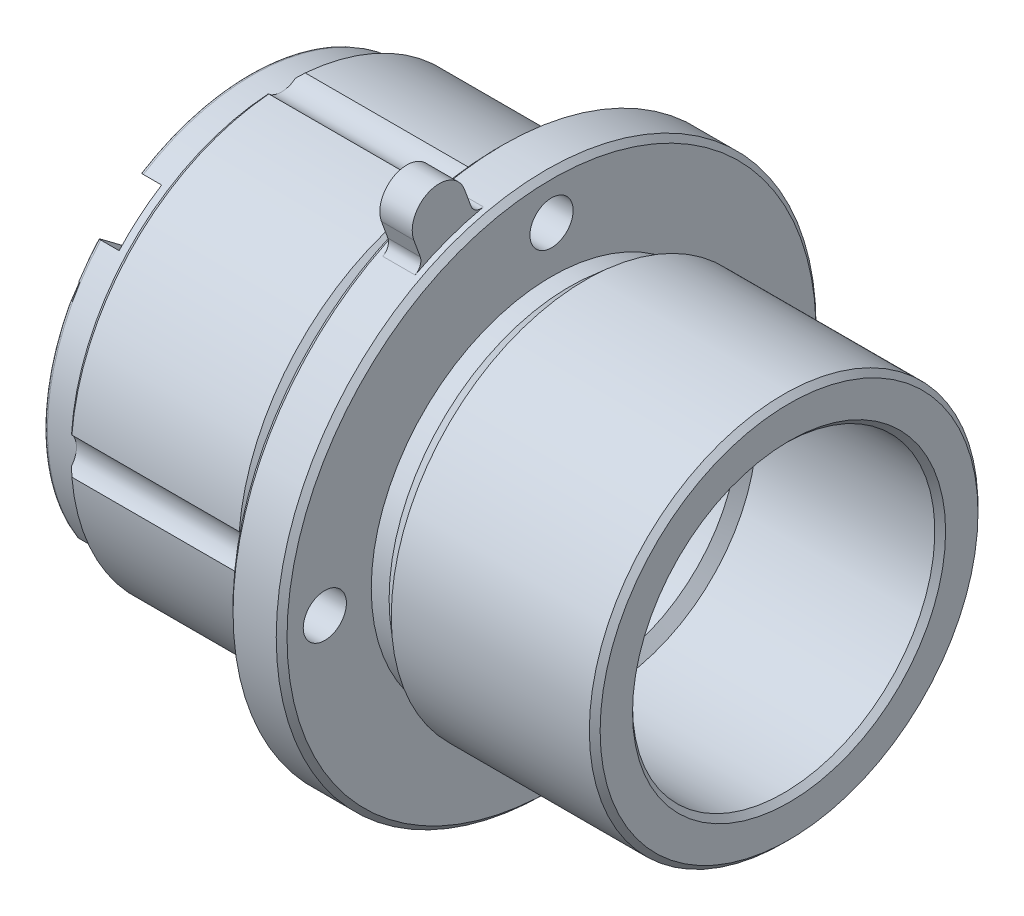
SolidWorks part; units mm, degrees
note: '?' marks a value the reader was unsure of.
ref_plane "Plane1" through (0, 0, 0) normal (0, 0, 1) x (1, 0, 0)
ref_plane "Plane2" through (0, 0, 0) normal (0, 1, 0) x (1, 0, 0)
ref_plane "Plane3" through (0, 0, 0) normal (1, 0, 0) x (0, 0, -1)
sketch "Sketch1" plane through (0, 0, 0) normal (0, 0, 1) x (1, 0, 0)
  line L0 (0, 35.56) -> (0, 48.26)
  line L1 (0, 48.26) -> (7.62, 48.26)
  line L2 (7.62, 48.26) -> (7.62, 50.8)
  line L3 (7.62, 50.8) -> (48.26, 50.8)
  line L4 (48.26, 50.8) -> (50.8, 48.26)
  line L5 (50.8, 48.26) -> (58.42, 48.26)
  line L6 (58.42, 48.26) -> (58.42, 63.5)
  line L7 (58.42, 63.5) -> (71.12, 63.5)
  line L8 (71.12, 63.5) -> (71.12, 42.4161)
  line L9 (71.12, 42.4161) -> (75.3191, 42.4161)
  line L10 (75.3191, 42.4161) -> (79.1291, 45.72)
  line L11 (79.1291, 45.72) -> (127, 45.72)
  line L12 (127, 45.72) -> (127, 35.56)
  line L13 (127, 35.56) -> (83.82, 35.56)
  line L14 (83.82, 35.56) -> (81.915, 33.02)
  line L15 (81.915, 33.02) -> (63.5, 33.02)
  line L16 (63.5, 33.02) -> (63.5, 30.48)
  line L17 (63.5, 30.48) -> (38.1, 30.48)
  line L18 (38.1, 30.48) -> (38.1, 38.1)
  line L19 (38.1, 38.1) -> (10.16, 38.1)
  line L20 (10.16, 38.1) -> (10.16, 35.56)
  line L21 (10.16, 35.56) -> (0, 35.56)
  line L22 (0, 0) -> (127, 0) construction
revolve "Base-Revolve" add sketch "Sketch1" angle 360 about L22
chamfer "Chamfer1" distance 1.27 angle 45 7 edges at (38.1, 0, 30.48) (127, 0, 35.56) (127, 0, 45.72) (71.12, 0, 63.5) (58.42, 0, 63.5) (7.62, 0, 50.8) (0, 0, 35.56)
fillet "Fillet1" radius 0.762 1 edges at (0, 0, 48.26)
sketch "Sketch2" plane through (71.12, 0, 0) normal (1, 0, 0) x (0, 0, -1)
  circle A0 centre (53.34, 0) radius 5.08
extrude "Cut-Extrude1" cut sketch "Sketch2" against normal through all
ref_axis "Axis1" through (-50, 0, 0) along (1, 0, 0)?
pattern_circular "CirPattern1" count 4 every 90 about axis through (0, 0, 0) along (1, 0, 0) of "Cut-Extrude1"
sketch "Sketch5" plane through (0, 0, 0) normal (-1, 0, 0) x (0, 0, 1)
  line L0 (0, 0) -> (55.88, 55.88) construction
  line L1 (45.72, 55.88) -> (53.34, 45.72)
  line L2 (45.72, 55.88) -> (3.048, 23.876)
  line L3 (53.34, 45.72) -> (10.668, 13.716)
  line L4 (3.048, 23.876) -> (10.668, 13.716)
extrude "Cut-Extrude2" cut sketch "Sketch5" against normal blind 5.08
pattern_circular "CirPattern2" count 4 every 90 about axis through (0, 0, 0) along (1, 0, 0) of "Cut-Extrude2"
ref_plane "Plane4" through (68.58, 0, 0) normal (1, 0, 0) x (0, 0, -1)
sketch "Sketch7" plane through (68.58, 0, 0) normal (1, 0, 0) x (0, 0, -1)
  line L0 (0, 0) -> (-33.3756, 91.6986) construction
  line L1 (0, 0) -> (0, 53.34) construction
  line L2 (-29.8572, 63.4657) -> (-27.5765, 57.1996)
  line L3 (-17.9231, 67.8094) -> (-15.6424, 61.5432)
  circle A0 centre (0, 0) radius 63.5 construction
  arc A1 (-15.6424, 61.5432) -> (-27.5765, 57.1996) centre (0, 0) ccw
  arc A2 (-29.8572, 63.4657) -> (-17.9231, 67.8094) centre (-23.8901, 65.6375) cw
  dimension "D3" = 69.85
  dimension "D1" = 20
  dimension "D2" = 12.7
  dimension "D4" = 6.35
  dimension "D5" = 76.2
extrude "Boss-Extrude1" add sketch "Sketch7" against normal offset from surface (7.62 mm away) 2.54 up to face at (58.42, 0, -62.23)
fillet "Fillet2" radius 2.54 2 edges at (64.77, 61.5432, 15.6424) (64.77, 57.1996, 27.5765)
ref_plane "Plane5" through (68.58, 63.4657, 29.8572) normal (0, -0.9397, -0.342) x (-1, 0, 0)
sketch "Sketch6" plane through (0, 0, 0) normal (0, 0, 1) x (1, 0, 0)
  line L0 (0, 0) -> (1.27, 0) construction
  line L1 (-6.3418, 0) -> (132.08, 0)
  line L2 (-6.3418, 0) -> (-6.3418, 76.2)
  line L3 (-6.3418, 76.2) -> (132.08, 76.2)
  line L4 (132.08, 0) -> (132.08, 76.2)
  dimension "D1" = 76.2
